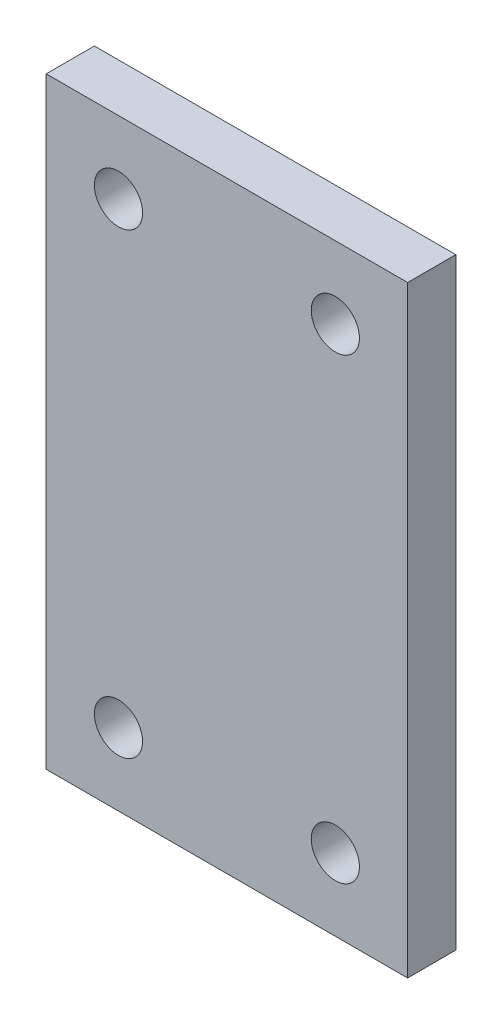
SolidWorks part; units mm, degrees
ref_plane "Front Plane" through (0, 0, 0) normal (0, 0, 1) x (1, 0, 0)
ref_plane "Top Plane" through (0, 0, 0) normal (0, 1, 0) x (1, 0, 0)
ref_plane "Right Plane" through (0, 0, 0) normal (1, 0, 0) x (0, 0, -1)
sketch "Sketch1" plane through (0, 0, 0) normal (0, 0, 1) x (1, 0, 0)
  line L0 (-29.5941, 119.0334) -> (-29.5941, 0.3078) construction
  line L1 (-48.6441, 94.1422) -> (-10.5441, 94.1422)
  line L2 (-48.6441, 94.1422) -> (-48.6441, 30.6422)
  line L3 (-48.6441, 30.6422) -> (-10.5441, 30.6422)
  line L4 (-10.5441, 94.1422) -> (-10.5441, 30.6422)
  line L5 (-48.6441, 94.1422) -> (-10.5441, 30.6422) construction
  line L6 (-48.6441, 30.6422) -> (-10.5441, 94.1422) construction
  line L7 (-82.748, 62.3922) -> (36.5001, 62.3922) construction
  line L8 (23.5598, 62.3922) -> (-95.6883, 62.3922) construction
  circle A0 centre (-41.0241, 38.2622) radius 2.54
  circle A1 centre (-18.1641, 38.2622) radius 2.54
  circle A2 centre (-18.1641, 86.5222) radius 2.54
  circle A3 centre (-41.0241, 86.5222) radius 2.54
  point P0 (-29.5941, 62.3922)
  dimension "D1" = 7.62
  dimension "D2" = 7.62
  dimension "D3" = 38.1
  dimension "D4" = 63.5
extrude "Boss-Extrude1" add sketch "Sketch1" along normal blind 5.08
